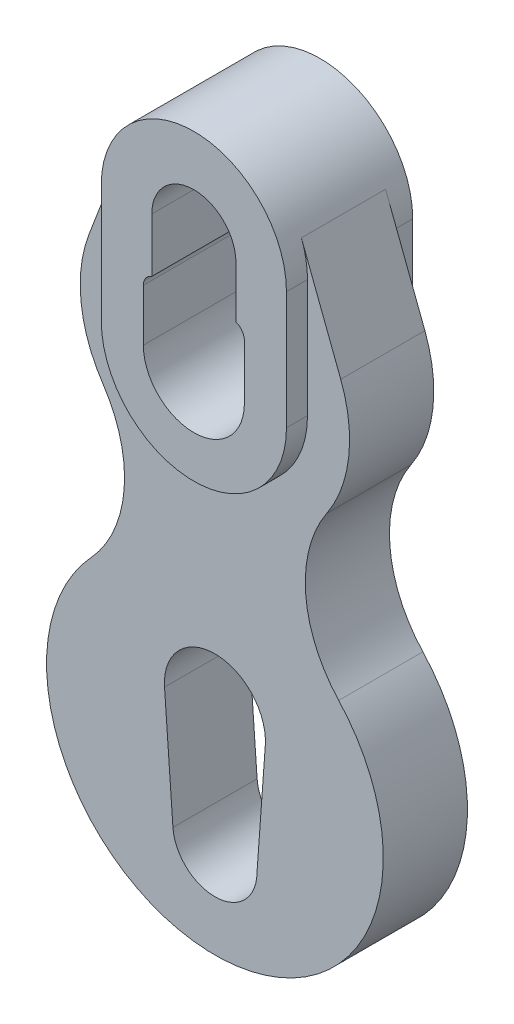
SolidWorks part; units mm, degrees
ref_plane "Front Plane" through (0, 0, 0) normal (0, 0, 1) x (1, 0, 0)
ref_plane "Top Plane" through (0, 0, 0) normal (0, 1, 0) x (1, 0, 0)
ref_plane "Right Plane" through (0, 0, 0) normal (1, 0, 0) x (0, 0, -1)
sketch "Sketch1" plane through (0, 0, 0) normal (0, 0, 1) x (1, 0, 0)
  line L0 (-696.923, 0) -> (-11.3146, 0) construction
  line L1 (0, -696.923) -> (0, -28) construction
  line L2 (11.9685, 9.1316) -> (10, -18)
  line L3 (-11.9693, 9.1429) -> (-9.9745, -18.7143)
  line L4 (11.306, 0) -> (34149.2274, 0) construction
  line L5 (0, -8) -> (0, 34149.2274) construction
  line L6 (0, 110) -> (0, 82) construction
  line L7 (22, 110) -> (22, 82)
  line L8 (-22, 110) -> (-22, 82)
  line L9 (10, 110) -> (10, 97.7631)
  line L10 (20.5491, 117.8571) -> (29.8896, 93.4286)
  line L11 (12, 94.9347) -> (12, 82)
  line L12 (-20.5491, 117.8571) -> (-29.8896, 93.4286)
  line L13 (-12, 94.3222) -> (-12, 82)
  line L14 (-10, 110) -> (-10, 97.1506)
  circle A0 centre (0, 0) radius 40
  arc A1 (-9.9745, -18.7143) -> (10, -18) centre (0, -18) ccw
  arc A2 (11.9685, 9.1316) -> (-11.9693, 9.1429) centre (0, 10) ccw
  arc A3 (22, 110) -> (-22, 110) centre (0, 110) ccw
  arc A4 (-22, 82) -> (22, 82) centre (0, 82) ccw
  arc A5 (10, 110) -> (-10, 110) centre (0, 110) ccw
  arc A6 (-12, 82) -> (12, 82) centre (0, 82) ccw
  arc A7 (-10, 97.1506) -> (-12, 94.3222) centre (-9, 94.3222) ccw
  arc A8 (10, 97.7631) -> (12, 94.9347) centre (9, 94.9347) cw
  arc A10 (26.5671, 64.1621) -> (29.4135, 27.108) centre (51.4737, 47.439) ccw
  arc A11 (-26.5671, 64.1621) -> (-29.4135, 27.108) centre (-51.4737, 47.439) cw
  arc A12 (-29.8896, 93.4286) -> (29.8896, 93.4286) centre (0, 82) ccw
  point P19 (0, 96)
  dimension "D1" = 80
  dimension "D2" = 20
  dimension "D3" = 24
  dimension "D6" = 22
  dimension "D9" = 20
  dimension "D10" = 24
  dimension "D12" = 3
  dimension "D13" = 3
  dimension "D14" = 30
  dimension "D4" = 10
  dimension "D5" = 28
  dimension "D7" = 28
  dimension "D8" = 128
extrude "Boss-Extrude1" add sketch "Sketch1" along normal mid plane 30 contours L8 A4 L7 A3 L9 A8 L11 A6 L13 A7 L14 A5 region at (21.1562, 96, 0)
extrude "Boss-Extrude3" add sketch "Sketch1<4>" along normal mid plane 20 contours A12 A11 A0 A10 | L12 A12 L10 A3 L7 A4 L8 | A0 A2 L2 A1 L3 region at (21.726, 114.0119, 0) region at (0, 45.1238, 0) region at (36.2056, 14.1394, 0)
sketch "Sketch1<4>" plane through (0, 0, 0) normal (0, 0, 1) x (1, 0, 0) same geometry as "Sketch1"
